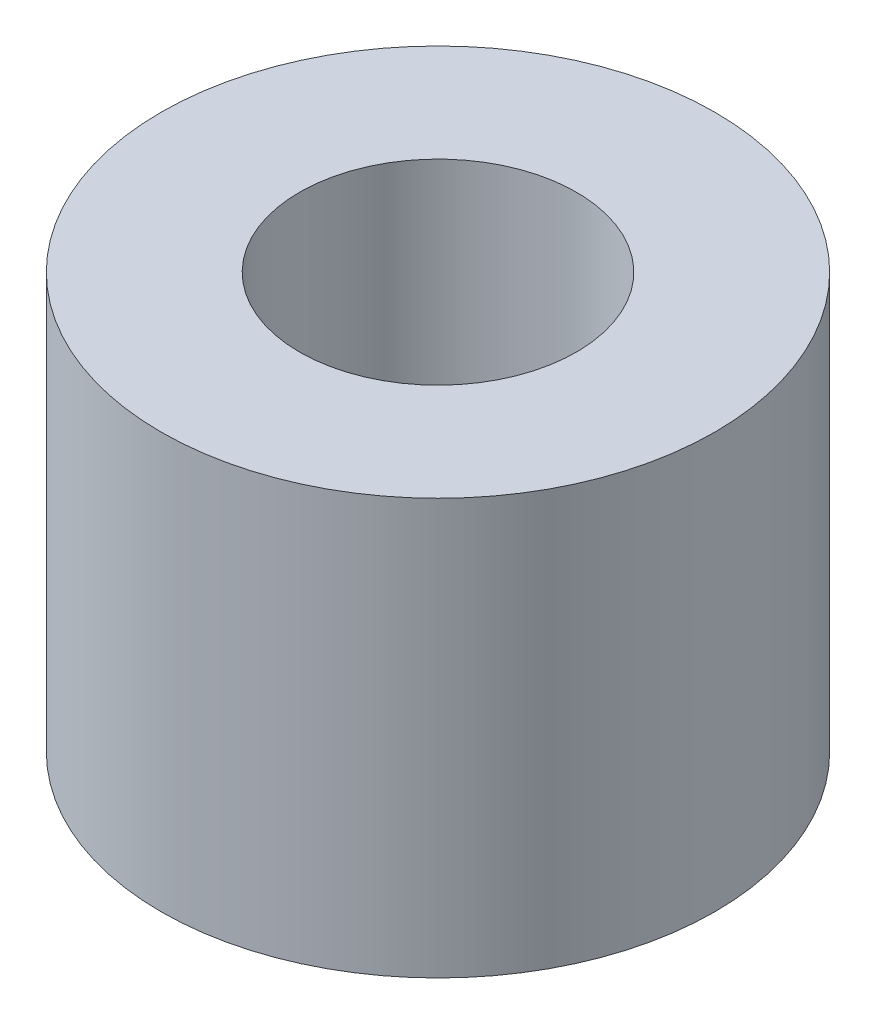
SolidWorks part; units mm, degrees
ref_plane "정면" through (0, 0, 0) normal (0, 0, 1) x (1, 0, 0)
ref_plane "윗면" through (0, 0, 0) normal (0, 1, 0) x (1, 0, 0)
ref_plane "우측면" through (0, 0, 0) normal (1, 0, 0) x (0, 0, -1)
sketch "스케치1" plane through (0, 0, 0) normal (0, 1, 0) x (1, 0, 0)
  circle A0 centre (0, 0) radius 6
  circle A1 centre (0, 0) radius 3
  dimension "D1" = 12
  dimension "D2" = 6
extrude "보스-돌출1" add sketch "스케치1" along normal blind 9 contours A0 | A1
